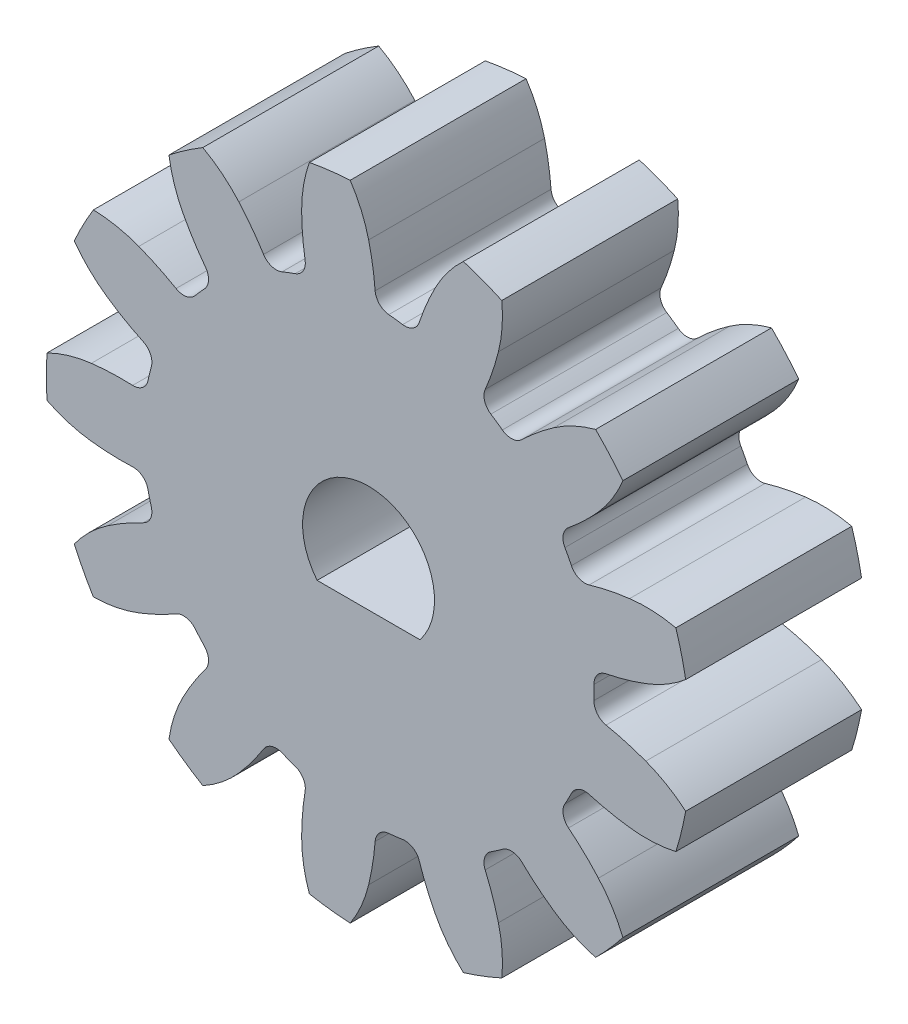
SolidWorks part; units mm, degrees
material "Plain Carbon Steel"
ref_plane "Front" through (0, 0, 0) normal (0, 0, 1) x (1, 0, 0)
ref_plane "Top" through (0, 0, 0) normal (0, 1, 0) x (1, 0, 0)
ref_plane "Right" through (0, 0, 0) normal (1, 0, 0) x (0, 0, -1)
sketch "Sketch1" plane through (0, 0, 0) normal (0, 0, 1) x (1, 0, 0)
  line L0 (0, 0) -> (6.35, 0) construction
  line L1 (6.35, 0) -> (7.3269, 0) construction
  circle A0 centre (0, 0) radius 6.35 construction
  circle A1 centre (0, 0) radius 7.3269
  dimension "pitch_diameter" = 12.7
  dimension "addendum" = 0.9769
extrude "BLANK DISK" add sketch "Sketch1" along normal mid plane 4
sketch "Sketch2" plane through (0, 0, 2) normal (0, 0, 1) x (1, 0, 0)
  line L0 (0, 0) -> (5.1288, 0) construction
  line L1 (5.1288, 0) -> (6.35, 0) construction
  line L2 (0, 0) -> (-7.3269, 0) construction
  line L3 (0, 0) -> (-6.4877, -3.405) construction
  line L4 (-6.6917, -2.9841) -> (-5.9381, -2.2499) construction
  line L5 (-5.9381, -2.2499) -> (-4.8614, -1.6345) construction
  line L6 (-7.312, -0.4675) -> (-6.3035, -0.7674) construction
  line L7 (-6.3035, -0.7674) -> (-5.0642, -0.8119) construction
  line L8 (-5.5814, -2.9294) -> (-5.9381, -2.2499) construction
  line L9 (-6.3035, -0.7674) -> (-6.3035, 0) construction
  line L12 (0, 0) -> (-6.3035, -0.7674) construction
  line L13 (0, 0) -> (-5.9381, -2.2499) construction
  line L14 (-5.9381, -2.2499) -> (-4.6429, -5.6681) construction
  line L15 (-6.3035, -0.7674) -> (-6.7452, 2.8611) construction
  line L16 (-5.9381, -2.2499) -> (-6.3035, -0.7674) construction
  line L17 (-4.9798, -1.2274) -> (-5.0642, -0.8119) construction
  line L18 (-4.9798, -1.2274) -> (-4.8614, -1.6345) construction
  circle A0 centre (0, 0) radius 6.35 construction
  circle A1 centre (0, 0) radius 5.1288 construction
  circle A2 centre (0, 0) radius 7.3269 construction
  arc A3 (-6.6917, -2.9841) -> (-7.312, -0.4675) centre (0, 0) cw
  arc A4 (-4.8614, -1.6345) -> (-5.0642, -0.8119) centre (0, 0) cw construction
  arc A6 (-6.6917, -2.9841) -> (-5.9381, -2.2499) centre (-4.2047, -4.7831) cw
  arc A7 (-7.312, -0.4675) -> (-6.3035, -0.7674) centre (-5.9459, 2.2812) ccw
  arc A8 (-5.9381, -2.2499) -> (-5.1228, -1.7827) centre (-2.6058, -7.1196) cw
  arc A9 (-6.3035, -0.7674) -> (-5.3644, -0.8022) centre (-5.616, 5.0931) ccw
  arc A10 (-5.1228, -1.7827) -> (-4.9393, -1.3813) centre (-5.2686, -1.4734) ccw
  arc A11 (-5.3644, -0.8022) -> (-5.0155, -1.0723) centre (-5.3499, -1.1438) cw
  arc A12 (-4.9393, -1.3813) -> (-5.0155, -1.0723) centre (0, 0) cw
  dimension "D12" = 3.0695
  dimension "D3" = 27.692
  dimension "D4" = 0.7674
  dimension "D5" = 0.7674
  dimension "D11" = 1.5269
  dimension "D14" = 9
  dimension "D15" = 9
  dimension "base_fillet" = 0.3419
  dimension "pitch_diameter" = 12.7
  dimension "deddendum" = 1.2212
extrude "GEAR TOOTH CUT" cut sketch "Sketch2" against normal through all
ref_axis "CENTER AXIS" through (0, 0, 50) along (0, 0, -1)
pattern_circular "GEAR TEETH REVOLVE" count 13 over 360 about axis through (0, 0, 50) along (0, 0, -1) of "GEAR TOOTH CUT"
sketch "Sketch4" plane through (0, 0, 2) normal (0, 0, 1) x (1, 0, 0)
  circle A0 centre (0, 0) radius 0.75
  dimension "D1" = 1.5
extrude "Hub Extrude" add sketch "Sketch4" along normal blind 0.635
sketch "Sketch3" plane through (0, 0, 2) normal (0, 0, 1) x (1, 0, 0)
  line L0 (-1.1689, -0.94) -> (1.1689, -0.94)
  arc A0 (1.1689, -0.94) -> (-1.1689, -0.94) centre (0, 0) ccw
  dimension "D1" = 3
  dimension "D2" = 0.94
extrude "HEX BORE CUT" cut sketch "Sketch3" against normal through all and the other way through all
equation "\"N_teeth\" = 13.000000"
equation "\"pitch_diameter\"= .5000000"
equation "\"Pd\"=\"N_teeth\"/\"pitch_diameter\""
equation "\"addendum\"=1.000/\"Pd\""
equation "\"face_width\"= 4mm"
equation "\"deddendum\"=1.250/\"Pd\""
equation "\"D3@Sketch2\" = 360/\"N_teeth\""
equation "\"tooth_thickness\"=1.571/\"Pd\""
equation "\"D4@Sketch2\" = \"tooth_thickness\"/2"
equation "\"D5@Sketch2\" = \"tooth_thickness\"/2"
equation "\"Pressure_Angle\"=14.500000"
equation "\"base_fillet\"=0.35/\"Pd\""
equation "\"D12@Sketch2\" = 2*\"tooth_thickness\""
equation "\"hub_diameter\"= 1.5mm"
equation "\"bore\"= 0.125000"
equation "\"hub_projection\"=0.250000"
equation "\"sss_diam\"=0.062500"
